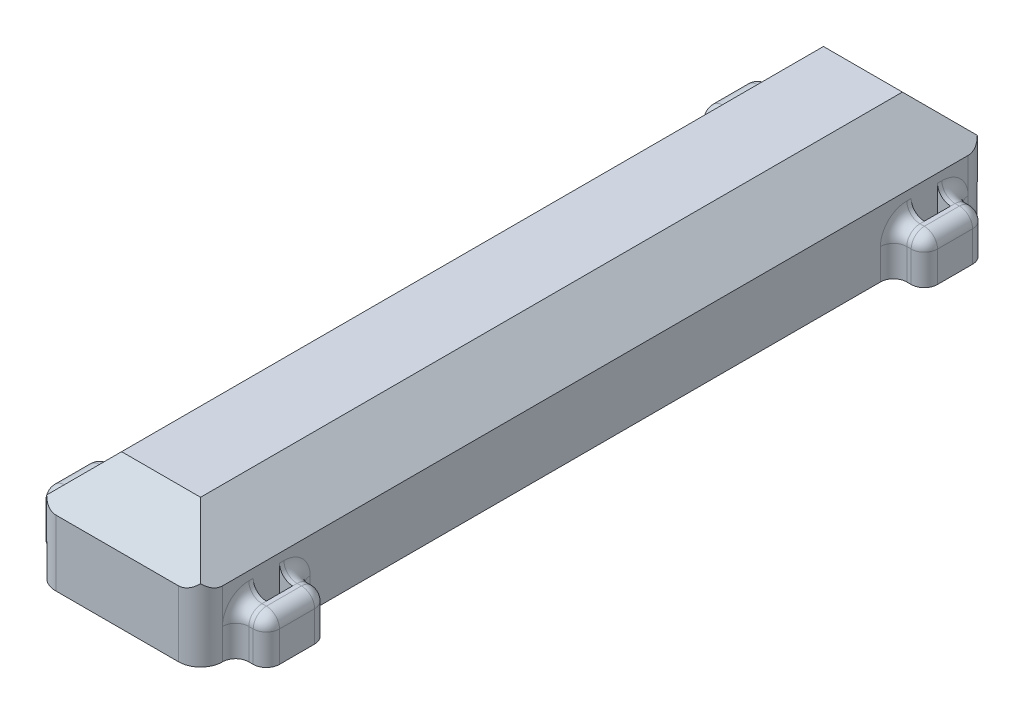
SolidWorks part; units mm, degrees
ref_plane "Front Plane" through (0, 0, 0) normal (0, 0, 1) x (1, 0, 0)
ref_plane "Top Plane" through (0, 0, 0) normal (0, 1, 0) x (1, 0, 0)
ref_plane "Right Plane" through (0, 0, 0) normal (1, 0, 0) x (0, 0, -1)
sketch "Sketch1" plane through (0, 0, 0) normal (0, 1, 0) x (1, 0, 0)
  line L1 (-19, -90) -> (19, -90)
  line L2 (-19, -90) -> (-19, 90)
  line L3 (-19, 90) -> (19, 90)
  line L4 (19, -90) -> (19, 90)
  line L5 (-19, -90) -> (19, 90) construction
  line L6 (-19, 90) -> (19, -90) construction
  point P0 (0, 0)
  dimension "D1" = 180
  dimension "D2" = 38
extrude "Boss-Extrude1" add sketch "Sketch1" along normal blind 25
sketch "Sketch2" plane through (0, 0, 0) normal (0, -1, 0) x (1, 0, 0)
  line L1 (-16, -87) -> (16, -87)
  line L2 (-16, -87) -> (-16, 87)
  line L3 (-16, 87) -> (16, 87)
  line L4 (16, -87) -> (16, 87)
  line L5 (-16, -87) -> (16, 87) construction
  line L6 (-16, 87) -> (16, -87) construction
  point P0 (0, 0)
  dimension "D1" = 32
  dimension "D2" = 174
extrude "Cut-Extrude1" cut sketch "Sketch2" against normal blind 22
chamfer "Chamfer1" distance 10 angle 45 8 edges at (0, 25, 90) (-19, 25, 0) (19, 25, 0) (0, 25, -90) (0, 22, -87) (-16, 22, 0) (0, 22, 87) (16, 22, 0)
fillet "Fillet1" radius 5 4 edges at (-19, 7.5, -90) (19, 7.5, -90) (-19, 7.5, 90) (19, 7.5, 90)
fillet "Fillet2" radius 2 4 edges at (-16, 6, -87) (16, 6, -87) (16, 6, 87) (-16, 6, 87)
sketch "Sketch3" plane through (19, 0, 0) normal (1, 0, 0) x (0, 0, -1)
  line L0 (-85, 0) -> (85, 0) construction
  line L1 (-68, 10) -> (-82, 10)
  line L2 (-68, 10) -> (-68, 0)
  line L3 (-68, 0) -> (-82, 0)
  line L4 (-82, 10) -> (-82, 0)
  line L5 (-68, 10) -> (-82, 0) construction
  line L6 (-68, 0) -> (-82, 10) construction
  line L7 (-85, 15) -> (-85, 0) construction
  line L8 (0, 0) -> (0, 15) construction
  line L9 (85, 15) -> (-85, 15) construction
  line L10 (68, 0) -> (82, 0)
  line L11 (82, 10) -> (82, 0)
  line L12 (68, 0) -> (82, 10) construction
  line L13 (68, 10) -> (82, 0) construction
  line L14 (68, 10) -> (68, 0)
  line L15 (68, 10) -> (82, 10)
  point P0 (-75, 5)
  point P18 (75, 5)
  dimension "D1" = 3
  dimension "D2" = 14
  dimension "D3" = 10
extrude "Boss-Extrude2" add sketch "Sketch3" along normal blind 7
sketch "Sketch4" plane through (-19, 0, 0) normal (-1, 0, 0) x (0, 0, 1)
  line L0 (-85, 0) -> (85, 0) construction
  line L1 (-68, 10.9395) -> (-82, 10.9395)
  line L2 (-68, 10.9395) -> (-68, 0)
  line L3 (-68, 0) -> (-82, 0)
  line L4 (-82, 10.9395) -> (-82, 0)
  line L5 (-68, 10.9395) -> (-82, 0) construction
  line L6 (-68, 0) -> (-82, 10.9395) construction
  line L7 (-85, 15) -> (-85, 0) construction
  line L8 (0, 15) -> (0, 0) construction
  line L9 (85, 15) -> (-85, 15) construction
  line L10 (68, 0) -> (82, 10.9395) construction
  line L11 (68, 10.9395) -> (82, 0) construction
  line L12 (82, 10.9395) -> (82, 0)
  line L13 (68, 0) -> (82, 0)
  line L14 (68, 10.9395) -> (68, 0)
  line L15 (68, 10.9395) -> (82, 10.9395)
  point P0 (-75, 5.4697)
  point P18 (75, 5.4697)
  dimension "D1" = 3
  dimension "D2" = 14
  dimension "D3" = 10.9395
extrude "Boss-Extrude3" add sketch "Sketch4" along normal blind 7
fillet "Fillet3" radius 3 32 edges at (-26, 5.4697, 82) (-26, 10.9395, 75) (-26, 5.4697, 68) (-26, 5.4697, -68) (-26, 10.9395, -75) (-26, 5.4697, -82) (26, 10, -75) (26, 5, -82) (26, 5, -68) (26, 5, 68) (26, 10, 75) (26, 5, 82) (22.5, 10, -82) (22.5, 10, -68) (22.5, 10, 68) (22.5, 10, 82) (-22.5, 10.9395, 82) (-22.5, 10.9395, 68) (-22.5, 10.9395, -68) (-22.5, 10.9395, -82) (19, 5, 68) (19, 5, 82) (19, 5, -82) (19, 5, -68) (-19, 5.4697, 82) (-19, 5.4697, 68) (-19, 5.4697, -68) (-19, 5.4697, -82) (19, 10, 75) (19, 10, -75) (-19, 10.9395, 75) (-19, 10.9395, -75)
sketch "Sketch5" plane through (0, 0, 0) normal (0, -1, 0) x (1, 0, 0)
  line L5 (0, 90) -> (0, 0) construction
  line L6 (-14, 90) -> (14, 90) construction
  line L7 (-19, 0) -> (19, 0) construction
  line L8 (-19, -65) -> (-19, 65) construction
  line L9 (19, 65) -> (19, -65) construction
  line L22 (22, 72) -> (19, 72)
  line L23 (19, 78) -> (19, 72)
  line L24 (22, 78) -> (19, 78)
  line L25 (22, 78) -> (22, 72)
  line L26 (-22, -72) -> (-19, -72)
  line L27 (-19, -78) -> (-19, -72)
  line L28 (-22, -78) -> (-19, -78)
  line L29 (-22, -78) -> (-22, -72)
  line L30 (22, -78) -> (22, -72)
  line L39 (-23, 82) -> (-22, 82) construction
  line L40 (-22, 78) -> (-19, 78)
  line L41 (-22, 78) -> (-22, 72)
  line L42 (-22, 72) -> (-19, 72)
  line L43 (-19, 78) -> (-19, 72)
  line L44 (22, -78) -> (19, -78)
  line L45 (19, -78) -> (19, -72)
  line L46 (22, -72) -> (19, -72)
  point P18 (0, 0)
  dimension "D1" = 4
  dimension "D2" = 3
  dimension "D3" = 6
extrude "Cut-Extrude2" cut sketch "Sketch5" against normal through all
